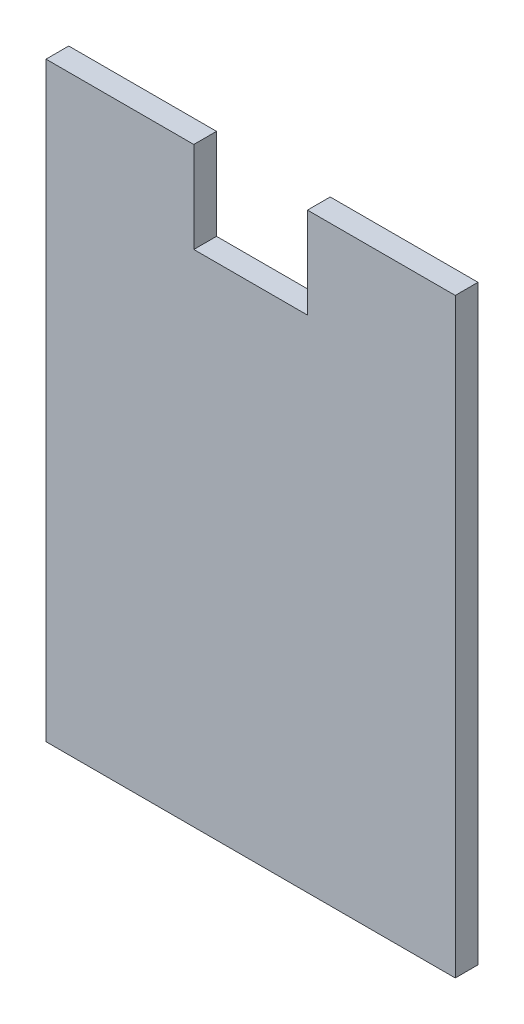
SolidWorks part; units mm, degrees
ref_plane "Front Plane" through (0, 0, 0) normal (0, 0, 1) x (1, 0, 0)
ref_plane "Top Plane" through (0, 0, 0) normal (0, 1, 0) x (1, 0, 0)
ref_plane "Right Plane" through (0, 0, 0) normal (1, 0, 0) x (0, 0, -1)
sketch "Sketch1" plane through (0, 0, 0) normal (0, 0, 1) x (1, 0, 0)
  line L0 (0, -262.711) -> (0, 262.711) construction
  line L1 (114.3, -165.1) -> (-114.3, -165.1)
  line L2 (114.3, -165.1) -> (114.3, 165.1)
  line L3 (114.3, 165.1) -> (31.75, 165.1)
  line L4 (-114.3, -165.1) -> (-114.3, 165.1)
  line L5 (114.3, -165.1) -> (-114.3, 165.1) construction
  line L6 (114.3, 165.1) -> (-114.3, -165.1) construction
  line L7 (-31.75, 114.3) -> (31.75, 114.3)
  line L8 (-31.75, 114.3) -> (-31.75, 165.1)
  line L9 (31.75, 114.3) -> (31.75, 165.1)
  line L10 (-31.75, 165.1) -> (-114.3, 165.1)
  point P0 (0, 0)
  point P9 (0, 0)
  point P12 (0, 114.3)
  dimension "D1" = 330.2
  dimension "D2" = 228.6
  dimension "D3" = 63.5
  dimension "D4" = 50.8
extrude "Boss-Extrude1" add sketch "Sketch1" along normal mid plane 12.7
